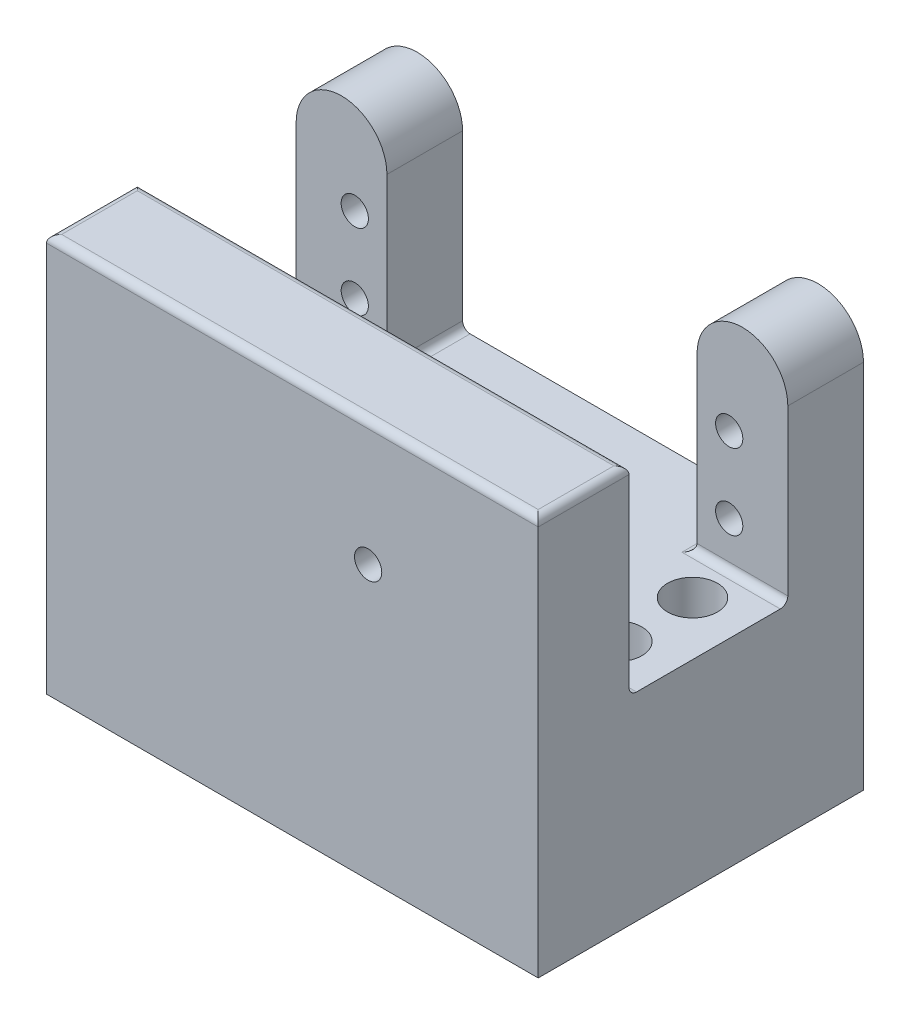
SolidWorks part; units mm, degrees
ref_plane "Front Plane" through (0, 0, 0) normal (0, 0, 1) x (1, 0, 0)
ref_plane "Top Plane" through (0, 0, 0) normal (0, 1, 0) x (1, 0, 0)
ref_plane "Right Plane" through (0, 0, 0) normal (1, 0, 0) x (0, 0, -1)
sketch "Sketch1" plane through (0, 0, 0) normal (0, 0, 1) x (1, 0, 0)
  line L0 (0, 25.9884) -> (0, -27.0349) construction
  line L1 (-6, 14.3023) -> (-6, -20.6977)
  line L2 (6, 14.3023) -> (6, -20.6977)
  line L3 (-6, -20.6977) -> (6, -20.6977)
  arc A0 (-6, 14.3023) -> (6, 14.3023) centre (0, 14.3023) cw
  dimension "D1" = 35
  dimension "D2" = 12
extrude "Boss-Extrude1" add sketch "Sketch1" along normal blind 10
sketch "Sketch2" plane through (0, 0, 10) normal (0, 0, 1) x (1, 0, 0)
  line L0 (6, -20.6977) -> (6, 14.3023) construction
  line L1 (-6, -20.6977) -> (6, -20.6977)
  line L2 (-6, -20.6977) -> (-6, -8.4477)
  line L3 (-6, -8.4477) -> (6, -8.4477)
  line L4 (6, -20.6977) -> (6, -8.4477)
  dimension "D1" = 12.25
extrude "Boss-Extrude2" add sketch "Sketch2" along normal blind 21 contours L3 L4 L1 L2
sketch "Sketch4" plane through (0, 0, 31) normal (0, 0, 1) x (1, 0, 0)
  line L1 (6, -20.6977) -> (-59, -20.6977)
  line L2 (6, -20.6977) -> (6, 17.9393)
  line L3 (6, 17.9393) -> (-59, 17.9393)
  line L4 (-59, -20.6977) -> (-59, 17.9393)
  dimension "D1" = 65
extrude "Boss-Extrude3" add sketch "Sketch4" along normal blind 12
ref_plane "Plane1" through (-26.5, 0, 0) normal (-1, 0, 0) x (0, 0, 1)
sketch "Sketch11" plane through (0, 0, 0) normal (0, 0, -1) x (-1, 0, 0)
  circle A0 centre (51.25, 8) radius 1.5
  circle A1 centre (51.25, -2) radius 1.5
  circle A3 centre (1.75, 7.5522) radius 1.5
  circle A4 centre (1.75, -2.4478) radius 1.5
  dimension "D1" = 49.5
  dimension "D4" = 3
  dimension "D5" = 3
  dimension "D6" = 3
  dimension "D7" = 3
  dimension "D2" = 10
  dimension "D3" = 49.5
  dimension "D8" = 10
mirror "Mirror2" about plane through (-26.5, 0, 0) normal (-1, 0, 0) of "Boss-Extrude2"
mirror "Mirror3" about plane through (-26.5, 0, 0) normal (-1, 0, 0) of "Boss-Extrude1"
hole_wizard "Ø3.6 (3.6) Diameter Hole1" positions "Sketch14" profile "Sketch15" hole size "Ø3.6" standard "ANSI Metric"
sketch "Sketch14" plane through (0, 0, 0) normal (0, 0, -1) x (-1, 0, 0)
  point P0 (1.75, 7.5522)
  point P3 (1.75, -2.4478)
  point P6 (51.25, 8)
  point P9 (51.25, -2)
sketch "Sketch15" plane through (-1.75, 7.5522, 0) normal (1, 0, 0) x (0, 1, 0)
  line L0 (0, 0) -> (0, 11.0815)
  line L1 (0, 11.0815) -> (1.8, 10)
  line L2 (1.8, 10) -> (1.8, 0)
  line L5 (1.8, 0) -> (0, 0)
  line L10 (0, 11.0815) -> (-1.8, 10) construction
  line L11 (0, -6.35) -> (0, 107.95) construction
  dimension "Hole Dia." = 3.6
  dimension "Hole Depth" = 10
  dimension "Drill Angle" = 118
hole_wizard "Ø3.6 (3.6) Diameter Hole2" positions "Sketch19" profile "Sketch20" hole size "Ø3.6" standard "ANSI Metric"
sketch "Sketch19" plane through (0, 0, 43) normal (0, 0, 1) x (1, 0, 0)
  point P0 (-16.4816, 1.4017)
sketch "Sketch20" plane through (-16.4816, 1.4017, 43) normal (1, 0, 0) x (0, -1, 0)
  line L0 (0, 0) -> (0, 13.0815)
  line L1 (0, 13.0815) -> (1.8, 12)
  line L2 (1.8, 12) -> (1.8, 0)
  line L5 (1.8, 0) -> (0, 0)
  line L10 (0, 13.0815) -> (-1.8, 12) construction
  line L11 (0, -6.35) -> (0, 107.95) construction
  dimension "Hole Dia." = 3.6
  dimension "Hole Depth" = 12
  dimension "Drill Angle" = 118
sketch "Sketch21" plane through (0, 0, 31) normal (0, 0, -1) x (-1, 0, 0)
  line L1 (6, -8.4477) -> (47, -8.4477)
  line L2 (6, -8.4477) -> (6, -20.6977)
  line L3 (6, -20.6977) -> (47, -20.6977)
  line L4 (47, -8.4477) -> (47, -20.6977)
extrude "Boss-Extrude4" add sketch "Sketch21" along normal up to surface (31 mm away) up to face at (-3.55, 7.5522, 0)
sketch "Sketch23" plane through (0, -20.6977, 0) normal (0, -1, 0) x (1, 0, 0)
  line L1 (-59, 43) -> (6, 43)
  line L2 (-59, 43) -> (-59, 0)
  line L3 (-59, 0) -> (6, 0)
  line L4 (6, 43) -> (6, 0)
extrude "Boss-Extrude6" add sketch "Sketch23" along normal blind 14
sketch "Sketch24" plane through (0, -34.6977, 0) normal (0, -1, 0) x (-1, 0, 0)
  line L6 (-6, 0) -> (-6, -43) construction
  circle A0 centre (1.1, -25.5) radius 3
  circle A2 centre (51.9, -25.5) radius 3
  circle A4 centre (1.1, -15.5) radius 3
  circle A5 centre (51.9, -15.5) radius 3
  point P10 (0, 0)
  dimension "D4" = 6
  dimension "D5" = 6
  dimension "D1" = 10
  dimension "D2" = 10
  dimension "D8" = 7.1
fillet "Fillet1" radius 1 9 edges at (-26.5, 17.9393, 43) (-26.5, 17.9393, 31) (6, 17.9393, 37) (-59, 17.9393, 37) (-53, -8.4477, 10) (0, -8.4477, 10) (-6, -8.4477, 5) (-47, -8.4477, 5) (-26.5, -8.4477, 31)
hole_wizard "Ø6.6 (6.6) Diameter Hole1" positions "Sketch25" profile "Sketch26" hole size "Ø6.6" standard "ANSI Metric" end condition through all
sketch "Sketch25" plane through (0, -34.6977, 0) normal (0, -1, 0) x (-1, 0, 0)
  point P0 (1.1, -15.5)
  point P3 (1.1, -25.5)
  point P6 (51.9, -15.5)
  point P9 (51.9, -25.5)
sketch "Sketch26" plane through (-1.1, -34.6977, 15.5) normal (1, 0, 0) x (0, 0, -1)
  line L0 (0, 0) -> (0, 55)
  line L1 (0, 55) -> (3.3, 55)
  line L2 (3.3, 55) -> (3.3, 0)
  line L5 (3.3, 0) -> (0, 0)
  line L11 (0, -6.35) -> (0, 107.95) construction
  dimension "Thru Hole Dia." = 6.6
  dimension "Thru Hole Depth" = 55
